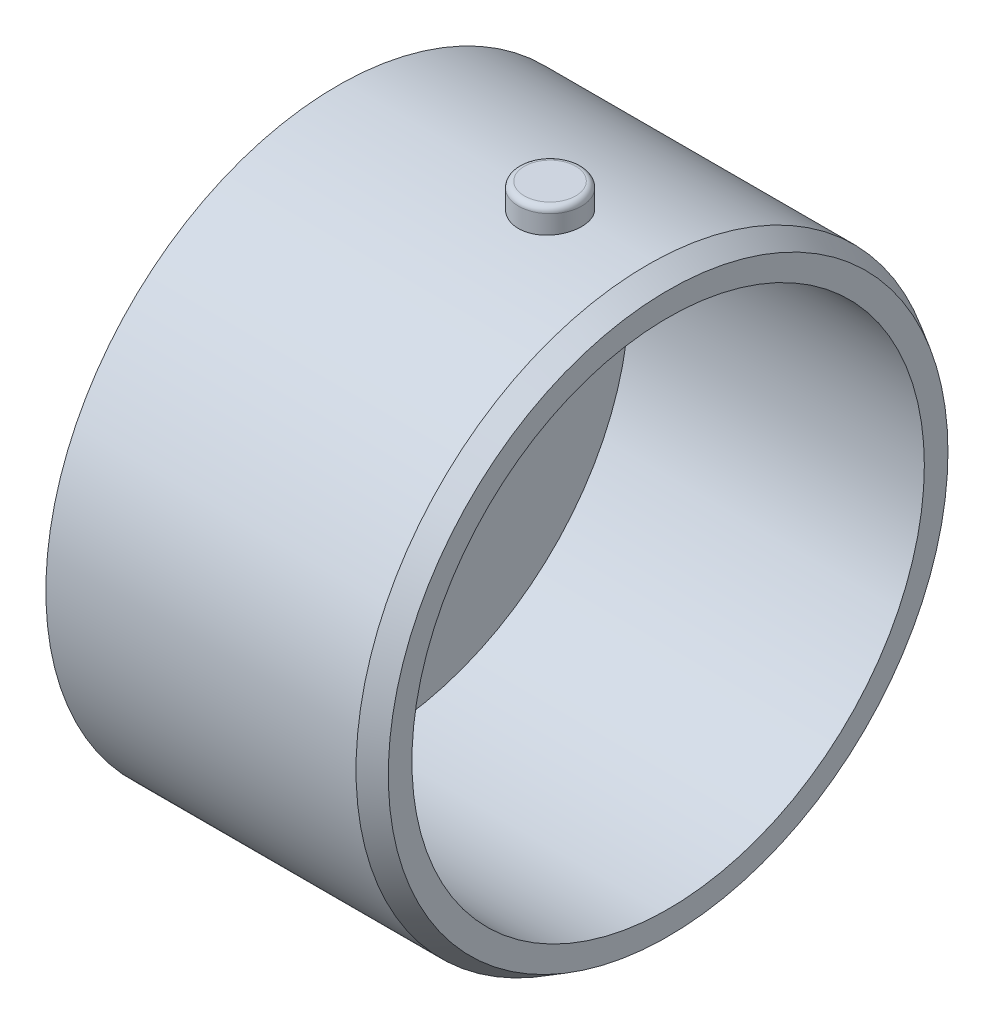
SolidWorks part; units mm, degrees
ref_plane "Front Plane" through (0, 0, 0) normal (1, 0, 0) x (0, 1, 0)
ref_plane "Top Plane" through (0, 0, 0) normal (0, 0, 1) x (0, 1, 0)
ref_plane "Right Plane" through (0, 0, 0) normal (0, 1, 0) x (-1, 0, 0)
sketch "Sketch1" plane through (0, 0, 0) normal (1, 0, 0) x (0, 1, 0)
  circle A0 centre (0, 0) radius 24.7
  circle A1 centre (0, 0) radius 21.7
  dimension "D1" = 49.4
  dimension "D2" = 3
extrude "Boss-Extrude1" add sketch "Sketch1" along normal blind 25
extrude "Boss-Extrude2" add sketch "Sketch1<2>" against normal blind 3 contours A0
sketch "Sketch1<2>" plane through (0, 0, 0) normal (1, 0, 0) x (0, 1, 0) same geometry as "Sketch1"
sketch "Sketch3" plane through (0, 0, 0) normal (0, 0, 1) x (0, 1, 0)
  line L0 (-32.9832, -15) -> (0, -15) construction
  line L1 (0, -15) -> (0, 0.3187) construction
  line L2 (-24.7, -25) -> (24.7, -25) construction
  line L3 (-26.7, -15) -> (-26.7, -17.675)
  line L4 (-26.7, -17.675) -> (-24.7, -17.675)
  line L5 (-24.7, 3) -> (-24.7, -25) construction
  line L6 (-26.7, -15) -> (-24.7, -15)
  line L7 (-24.7, -15) -> (-24.7, -17.675) construction
  line L8 (-24.7, -17.675) -> (-23.7, -17.675)
  line L9 (-23.7, -17.675) -> (-23.7, -15)
  line L10 (-23.7, -15) -> (-24.7, -15)
  dimension "D1" = 10
  dimension "D2" = 2.675
  dimension "D3" = 2
  dimension "D4" = 1
revolve "Revolve1" add sketch "Sketch3" angle 360 about L0
mirror "Mirror1" about plane through (0, 0, 0) normal (0, 1, 0) of "Revolve1"
fillet "Fillet1" radius 0.5 2 edges at (15, 26.7, -2.675) (15, -26.7, -2.675)
chamfer "Chamfer1" distance 1 angle 60 1 edges at (25, 0, -24.7) first distance on face at (25, 0, -24.7)
hole_wizard "CSK for M5 Countersunk Flat Head Screw1" positions "Sketch4" profile "Sketch5" countersink size "M5" standard "ISO" end condition through all
sketch "Sketch4" plane through (0, 0, 0) normal (1, 0, 0) x (0, 1, 0)
  point P0 (-12.5, 0)
  point P2 (12.5, 0)
  dimension "D1" = 25
  dimension "D2" = 12.5
sketch "Sketch5" plane through (0, -12.5, 0) normal (0, 1, 0) x (0, 0, -1)
  line L0 (0, 0) -> (0, 3)
  line L1 (0, 3) -> (2.125, 3)
  line L2 (2.125, 3) -> (2.125, 1.375)
  line L3 (2.125, 1.375) -> (3.5, 0)
  line L5 (3.5, 0) -> (0, 0)
  line L6 (-2.125, 1.375) -> (-3.5, 0) construction
  line L11 (0, -6.35) -> (0, 107.95) construction
  dimension "Thru Hole Dia." = 4.25
  dimension "Thru Hole Depth" = 3
  dimension "Near C'Sink Dia." = 7
  dimension "Near C'Sink Angle" = 90
sketch "Sketch7" plane through (0, 0, 0) normal (1, 0, 0) x (0, 1, 0)
  line L0 (-21.1161, 5) -> (21.1161, 5) construction
  circle A0 centre (0, 0) radius 21.7 construction
  text T0 "<b>7382-4916</b>" font "Century Gothic" height 5
  point P1 (0, 0)
  point P2 (21.0463, 5.2862)
  point P3 (-15.808, 4.3696)
  point P4 (-15.3281, 5.9694)
  dimension "D1" = 5
extrude "Cut-Extrude1" cut sketch "Sketch7" against normal blind 1
equation "\"D2@Sketch4\"=\"D1@Sketch4\"/2"
